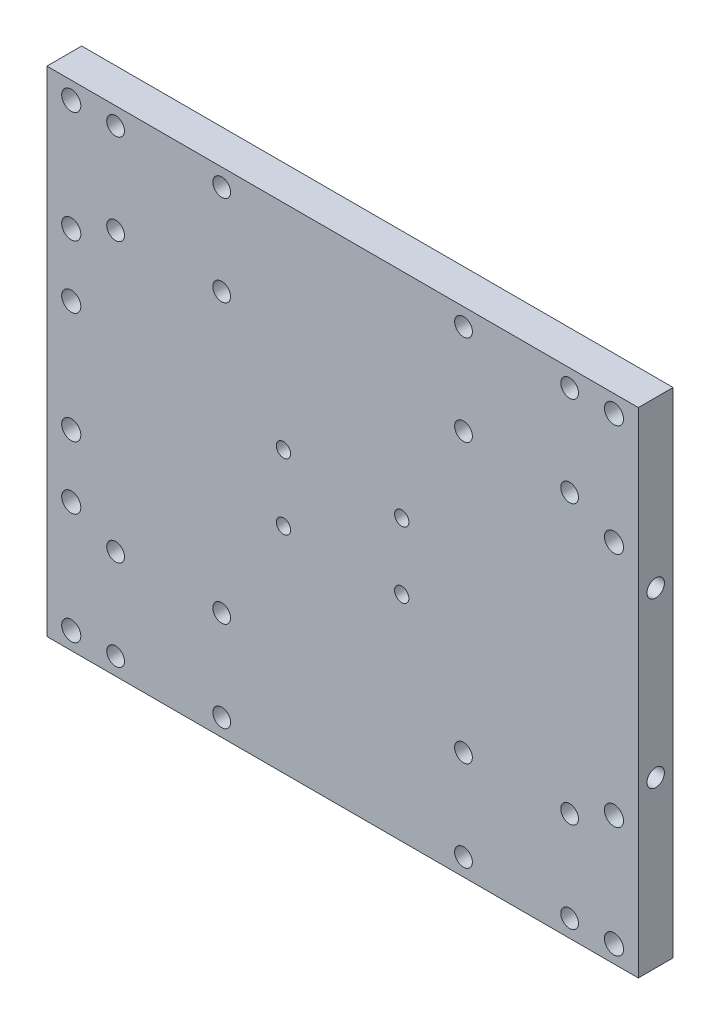
SolidWorks part; units mm, degrees
ref_plane "Front Plane" through (0, 0, 0) normal (0, 0, 1) x (1, 0, 0)
ref_plane "Top Plane" through (0, 0, 0) normal (0, 1, 0) x (1, 0, 0)
ref_plane "Right Plane" through (0, 0, 0) normal (1, 0, 0) x (0, 0, -1)
sketch "Sketch1" plane through (0, 0, 0) normal (0, 0, 1) x (1, 0, 0)
  line L1 (85, -71) -> (-85, -71)
  line L2 (85, -71) -> (85, 71)
  line L3 (85, 71) -> (-85, 71)
  line L4 (-85, -71) -> (-85, 71)
  line L5 (85, -71) -> (-85, 71) construction
  line L6 (85, 71) -> (-85, -71) construction
  point P0 (0, 0)
  dimension "D1" = 170
  dimension "D2" = 142
extrude "Boss-Extrude1" add sketch "Sketch1" along normal mid plane 10
sketch "Sketch2" plane through (0, 0, 5) normal (0, 0, 1) x (1, 0, 0)
  line L0 (-65.25, 71) -> (-65.25, -71) construction
  line L1 (65.25, -71) -> (65.25, 71) construction
  line L2 (-34.75, 71) -> (-34.75, -71) construction
  line L3 (34.75, -71) -> (34.75, 71) construction
  line L4 (70.6711, 66) -> (-71.3289, 66) construction
  line L5 (-71.3289, -66) -> (70.6711, -66) construction
  line L6 (70.6711, 40) -> (-71.3289, 40) construction
  line L7 (-71.3289, -40) -> (70.6711, -40) construction
  line L8 (85, 71) -> (-85, 71) construction
  line L9 (-85, -71) -> (85, -71) construction
  line L10 (-85, 71) -> (-85, -71) construction
  line L11 (85, -71) -> (85, 71) construction
  circle A0 centre (-65.25, 66) radius 2.55
  circle A1 centre (-34.75, 66) radius 2.55
  circle A2 centre (-34.75, 40) radius 2.55
  circle A3 centre (-65.25, 40) radius 2.55
  circle A4 centre (65.25, 66) radius 2.55
  circle A5 centre (65.25, 40) radius 2.55
  circle A6 centre (34.75, 40) radius 2.55
  circle A7 centre (34.75, 66) radius 2.55
  circle A8 centre (-65.25, -40) radius 2.55
  circle A9 centre (-34.75, -40) radius 2.55
  circle A10 centre (-34.75, -66) radius 2.55
  circle A11 centre (-65.25, -66) radius 2.55
  circle A12 centre (34.75, -40) radius 2.55
  circle A13 centre (65.25, -40) radius 2.55
  circle A14 centre (65.25, -66) radius 2.55
  circle A15 centre (34.75, -66) radius 2.55
  dimension "D1" = 5.1
  dimension "D2" = 5.1
  dimension "D3" = 5.1
  dimension "D4" = 5.1
  dimension "D5" = 5.1
  dimension "D6" = 5.1
  dimension "D7" = 5.1
  dimension "D8" = 5.1
  dimension "D9" = 5.1
  dimension "D10" = 5.1
  dimension "D11" = 5.1
  dimension "D12" = 5.1
  dimension "D13" = 5.1
  dimension "D14" = 5.1
  dimension "D15" = 5.1
  dimension "D16" = 5.1
  dimension "D17" = 5
  dimension "D18" = 5
  dimension "D19" = 26
  dimension "D20" = 26
  dimension "D21" = 30.5
  dimension "D22" = 30.5
  dimension "D23" = 19.75
  dimension "D24" = 19.75
extrude "Cut-Extrude1" cut sketch "Sketch2" against normal through all
sketch "Sketch3" plane through (0, 0, 5) normal (0, 0, 1) x (1, 0, 0)
  line L0 (-78, 71) -> (-78, -71) construction
  line L1 (85, 71) -> (-85, 71) construction
  line L2 (-85, -71) -> (85, -71) construction
  line L3 (78, 71) -> (78, -71) construction
  line L4 (-85, 66) -> (85, 66) construction
  line L5 (-85, 71) -> (-85, -71) construction
  line L6 (85, -71) -> (85, 71) construction
  line L7 (-85, 34) -> (85, 34) construction
  line L8 (-85, -34) -> (85, -34) construction
  line L9 (-85, -66) -> (85, -66) construction
  circle A0 centre (-78, 66) radius 2.75
  circle A1 centre (-78, 34) radius 2.75
  circle A2 centre (-78, -34) radius 2.75
  circle A3 centre (-78, -66) radius 2.75
  circle A4 centre (78, 66) radius 2.75
  circle A5 centre (78, 34) radius 2.75
  circle A6 centre (78, -34) radius 2.75
  circle A7 centre (78, -66) radius 2.75
  dimension "D7" = 5.5
  dimension "D8" = 5.5
  dimension "D9" = 5.5
  dimension "D10" = 5.5
  dimension "D11" = 5.5
  dimension "D12" = 5.5
  dimension "D13" = 5.5
  dimension "D14" = 5.5
  dimension "D1" = 5
  dimension "D2" = 32
  dimension "D3" = 5
  dimension "D4" = 32
  dimension "D5" = 7
  dimension "D6" = 7
extrude "Cut-Extrude2" cut sketch "Sketch3" against normal through all
sketch "Sketch4" plane through (0, 0, 5) normal (0, 0, 1) x (1, 0, 0)
  line L1 (-17, -9.5) -> (17, -9.5) construction
  line L2 (-17, -9.5) -> (-17, 9.5) construction
  line L3 (-17, 9.5) -> (17, 9.5) construction
  line L4 (17, -9.5) -> (17, 9.5) construction
  line L5 (-17, -9.5) -> (17, 9.5) construction
  line L6 (-17, 9.5) -> (17, -9.5) construction
  circle A0 centre (-17, 9.5) radius 2.05
  circle A1 centre (-17, -9.5) radius 2.05
  circle A2 centre (17, -9.5) radius 2.05
  circle A3 centre (17, 9.5) radius 2.05
  point P0 (0, 0)
  dimension "D3" = 4.1
  dimension "D4" = 4.1
  dimension "D5" = 4.1
  dimension "D6" = 4.1
  dimension "D1" = 34
  dimension "D2" = 19
extrude "Cut-Extrude3" cut sketch "Sketch4" against normal through all
sketch "Sketch5" plane through (85, 0, 0) normal (1, 0, 0) x (0, 0, -1)
  line L0 (0, 71) -> (0, -71) construction
  line L1 (-5, 71) -> (5, 71) construction
  line L2 (-5, -71) -> (5, -71) construction
  circle A0 centre (0, 23.6) radius 2.5
  circle A1 centre (0, -23.6) radius 2.5
  dimension "D1" = 5
  dimension "D2" = 5
  dimension "D3" = 23.6
  dimension "D4" = 23.6
extrude "Cut-Extrude4" cut sketch "Sketch5" against normal blind 10
sketch "Sketch6" plane through (0, 0, 5) normal (0, 0, 1) x (1, 0, 0)
  line L0 (-78, 34) -> (-78, -34) construction
  line L1 (-78, 0) -> (-85, 0) construction
  line L2 (-85, 71) -> (-85, -71) construction
  circle A0 centre (-78, 16) radius 2.75
  circle A1 centre (-78, -16) radius 2.75
  dimension "D1" = 5.5
  dimension "D2" = 5.5
  dimension "D3" = 16
  dimension "D4" = 16
extrude "Cut-Extrude5" cut sketch "Sketch6" against normal through all
equation "\"D23@Sketch2\"=5.75+14"
equation "\"D24@Sketch2\"=5.75+14"
equation "\"D6@Sketch4\"=\"D3@Sketch4\""
equation "\"D4@Sketch4\"=\"D3@Sketch4\""
equation "\"D5@Sketch4\"=\"D3@Sketch4\""
equation "\"D3@Sketch5\"=47.2/2"
equation "\"D4@Sketch5\"=47.2/2"
equation "\"D3@Sketch6\"=32/2"
equation "\"D4@Sketch6\"=32/2"
